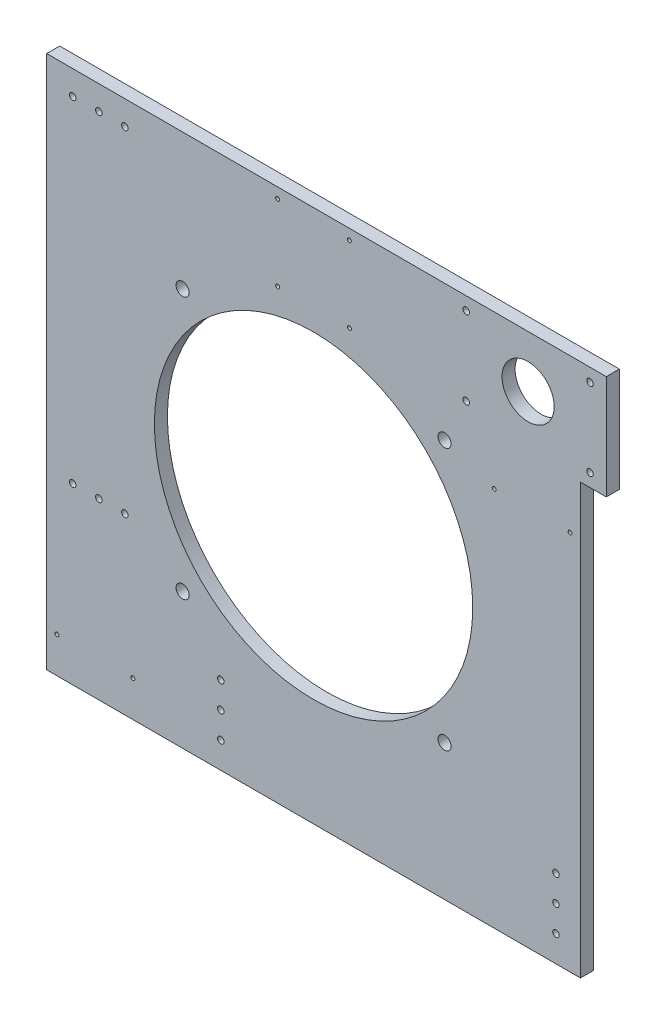
SolidWorks part; units mm, degrees
material "Perspex (TM) GS Acrylic Cast Sheet"
ref_plane "Front Plane" through (0, 0, 0) normal (0, 0, 1) x (1, 0, 0)
ref_plane "Top Plane" through (0, 0, 0) normal (0, 1, 0) x (1, 0, 0)
ref_plane "Right Plane" through (0, 0, 0) normal (1, 0, 0) x (0, 0, -1)
sketch "Sketch1" plane through (0, 0, 0) normal (0, 0, 1) x (1, 0, 0)
  line L1 (0, 0) -> (260.096, 0)
  line L2 (0, 0) -> (0, 260.096)
  line L3 (0, 260.096) -> (260.096, 260.096)
  line L4 (260.096, 0) -> (260.096, 260.096)
  dimension "D1" = 260.096
  dimension "D2" = 260.096
extrude "Boss-Extrude1" add sketch "Sketch1" along normal blind 6.35 contours L3 L4 L1 L2
sketch "Sketch2" plane through (0, 0, 6.35) normal (0, 0, 1) x (1, 0, 0)
  line L0 (-199848.9707, 50.896) -> (200294.6062, 50.896) construction
  line L1 (-199848.9707, 50.896) -> (200294.6062, 50.896) construction
  line L2 (130.048, 0) -> (130.048, 260.096) construction
  line L3 (0, 0) -> (260.096, 0) construction
  line L4 (0, 260.096) -> (260.096, 260.096) construction
  line L5 (260.096, 130.048) -> (0, 130.048) construction
  line L6 (0, 0) -> (0, 260.096) construction
  line L7 (260.096, 0) -> (260.096, 260.096) construction
  circle A0 centre (130.048, 130.048) radius 79.152 construction
  circle A1 centre (130.048, 130.048) radius 77.5645
  dimension "D1" = 1.5875
extrude "Cut-Extrude1" cut sketch "Sketch2" against normal through all
sketch "Sketch3" plane through (0, 0, 0) normal (0, 0, -1) x (-1, 0, 0)
  line L0 (-272.7, 209.296) -> (-272.7, 260.096) construction
  line L1 (-272.7, 209.296) -> (-272.7, 260.096)
  line L2 (-272.7, 209.296) -> (-260.096, 209.296)
  line L3 (-260.096, 0) -> (-260.096, 260.096) construction
  line L4 (-260.096, 209.296) -> (-260.096, 260.096)
  line L5 (-260.096, 260.096) -> (-272.7, 260.096)
extrude "Boss-Extrude2" add sketch "Sketch3" against normal up to surface (6.35 mm away) up to face at (207.6125, 130.048, 6.35)
sketch "Sketch5" plane through (0, 0, 6.35) normal (0, 0, 1) x (1, 0, 0)
  line L0 (260.096, 0) -> (0, 260.096) construction
  line L1 (260.096, 260.096) -> (0, 0) construction
  line L2 (0, 260.096) -> (272.7, 260.096) construction
  line L3 (260.096, 209.296) -> (260.096, 260.096) construction
  line L6 (0, 130.048) -> (260.096, 130.048) construction
  line L9 (0, 0) -> (0, 260.096) construction
  line L10 (260.096, 0) -> (260.096, 209.296) construction
  line L11 (0, 0) -> (260.096, 0) construction
  circle A0 centre (193.8746, 66.2214) radius 3.175
  circle A1 centre (130.048, 130.048) radius 77.5645 construction
  circle A2 centre (66.2214, 193.8746) radius 3.175
  circle A3 centre (193.8746, 193.8746) radius 3.175
  circle A4 centre (66.2214, 66.2214) radius 3.175
  point P3 (184.8944, 75.2016)
  dimension "D2" = 6.35
  dimension "D1" = 12.7
extrude "Cut-Extrude2" cut sketch "Sketch5" against normal through all
sketch "Sketch6" plane through (0, 0, 6.35) normal (0, 0, 1) x (1, 0, 0)
  circle A0 centre (264.7625, 253.746) radius 1.5875 construction
  circle A1 centre (264.7625, 215.646) radius 1.5875 construction
  circle A2 centre (204.4375, 253.746) radius 1.5875 construction
  circle A3 centre (204.4375, 215.646) radius 1.5875 construction
  circle A4 centre (264.7625, 253.746) radius 1.5875
  circle A5 centre (264.7625, 215.646) radius 1.5875
  circle A6 centre (204.4375, 253.746) radius 1.5875
  circle A7 centre (204.4375, 215.646) radius 1.5875
extrude "Cut-Extrude3" cut sketch "Sketch6" against normal through all
sketch "Sketch7" plane through (0, 0, 6.35) normal (0, 0, 1) x (1, 0, 0)
  circle A0 centre (248.189, 12.796) radius 1.5875 construction
  circle A1 centre (248.189, 25.496) radius 1.5875 construction
  circle A2 centre (248.189, 38.196) radius 1.5875 construction
  circle A3 centre (248.189, 12.796) radius 1.5875
  circle A4 centre (248.189, 25.496) radius 1.5875
  circle A5 centre (248.189, 38.196) radius 1.5875
  circle A6 centre (84.867, 12.796) radius 1.5875 construction
  circle A7 centre (84.867, 25.496) radius 1.5875 construction
  circle A8 centre (84.867, 38.196) radius 1.5875 construction
  circle A9 centre (12.7, 84.963) radius 1.5875 construction
  circle A10 centre (25.4, 84.963) radius 1.5875 construction
  circle A11 centre (38.1, 84.963) radius 1.5875 construction
  circle A12 centre (38.1, 248.285) radius 1.5875 construction
  circle A13 centre (25.4, 248.285) radius 1.5875 construction
  circle A14 centre (12.7, 248.285) radius 1.5875 construction
  circle A15 centre (84.867, 12.796) radius 1.5875
  circle A16 centre (84.867, 25.496) radius 1.5875
  circle A17 centre (84.867, 38.196) radius 1.5875
  circle A18 centre (12.7, 84.963) radius 1.5875
  circle A19 centre (25.4, 84.963) radius 1.5875
  circle A20 centre (38.1, 84.963) radius 1.5875
  circle A21 centre (38.1, 248.285) radius 1.5875
  circle A22 centre (25.4, 248.285) radius 1.5875
  circle A23 centre (12.7, 248.285) radius 1.5875
extrude "Cut-Extrude4" cut sketch "Sketch7" against normal through all
sketch "Sketch8" plane through (0, 0, 0) normal (0, 0, -1) x (-1, 0, 0)
  circle A0 centre (-255.0541, 185.4454) radius 0.9525 construction
  circle A1 centre (-218.0717, 185.4454) radius 0.9525 construction
  circle A2 centre (-147.5486, 218.0717) radius 0.9525 construction
  circle A3 centre (-147.5486, 255.0541) radius 0.9525 construction
  circle A4 centre (-112.5474, 218.0717) radius 0.9525 construction
  circle A5 centre (-112.5474, 255.0541) radius 0.9525 construction
  circle A6 centre (-5.0419, 17.5006) radius 0.9525 construction
  circle A7 centre (-42.0243, 17.5006) radius 0.9525 construction
  circle A8 centre (-255.0541, 185.4454) radius 0.9525
  circle A9 centre (-218.0717, 185.4454) radius 0.9525
  circle A10 centre (-147.5486, 218.0717) radius 0.9525
  circle A11 centre (-147.5486, 255.0541) radius 0.9525
  circle A12 centre (-112.5474, 218.0717) radius 0.9525
  circle A13 centre (-112.5474, 255.0541) radius 0.9525
  circle A14 centre (-5.0419, 17.5006) radius 0.9525
  circle A15 centre (-42.0243, 17.5006) radius 0.9525
extrude "Cut-Extrude5" cut sketch "Sketch8" against normal through all
sketch "Sketch9" plane through (0, 0, 0) normal (0, 0, -1) x (-1, 0, 0)
  circle A0 centre (-234.6, 234.696) radius 18.161 construction
  circle A1 centre (-234.6, 234.696) radius 18.161 construction
  circle A2 centre (-234.6, 234.696) radius 12.7
  dimension "D1" = 25.4
extrude "Cut-Extrude6" cut sketch "Sketch9" against normal through all
